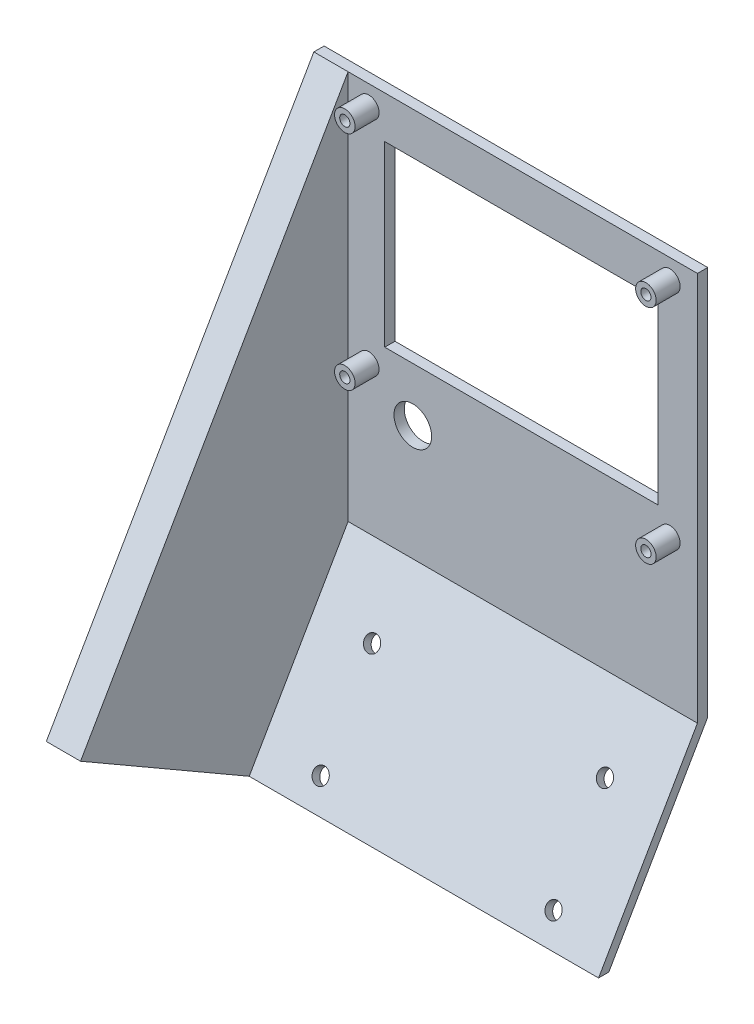
SolidWorks part; units mm, degrees
ref_plane "Front Plane" through (0, 0, 0) normal (0, 0, 1) x (1, 0, 0)
ref_plane "Top Plane" through (0, 0, 0) normal (0, 1, 0) x (1, 0, 0)
ref_plane "Right Plane" through (0, 0, 0) normal (1, 0, 0) x (0, 0, -1)
sketch "Sketch1" plane through (0, 0, 0) normal (0, 0, 1) x (1, 0, 0)
  line L0 (0, 0) -> (0, 113.73)
  line L1 (0, 0) -> (102, 0)
  line L2 (102, 0) -> (102, 113.73)
  line L3 (0, 113.73) -> (102, 113.73)
  line L5 (10.7, 101.42) -> (90.5, 101.42)
  line L6 (10.7, 101.42) -> (10.7, 49.42)
  line L7 (10.7, 49.42) -> (90.5, 49.42)
  line L8 (90.5, 101.42) -> (90.5, 49.42)
  circle A0 centre (6.05, 107.87) radius 3
  circle A1 centre (93.95, 107.87) radius 3
  circle A2 centre (6.05, 42.97) radius 3
  circle A3 centre (93.95, 42.97) radius 3
  circle A4 centre (18.9, 33.699) radius 5.5
  dimension "D7" = 6
  dimension "D10" = 11
  dimension "D1" = 87.9
  dimension "D2" = 64.9
  dimension "D3" = 102
  dimension "D4" = 6.05
  dimension "D5" = 113.73
  dimension "D6" = 5.86
  dimension "D8" = 18.9
  dimension "D9" = 80.031
  dimension "D11" = 12.31
  dimension "D12" = 10.7
  dimension "D13" = 52
  dimension "D14" = 79.8
extrude "Boss-Extrude1" add sketch "Sketch1" along normal blind 3 contours L3 L0 L1 L2 A4 A3 A2 A1 A0 L5 L8 L7 L6 | A0 | A1 region at (51.666, 46.2484, 0)
extrude "Boss-Extrude2" add sketch "Sketch1<3>" along normal blind 10 contours A0 | A2 | A3 | A1
sketch "Sketch1<3>" plane through (0, 0, 0) normal (0, 0, 1) x (1, 0, 0) same geometry as "Sketch1"
sketch "Sketch2" plane through (0, 0, 10) normal (0, 0, 1) x (1, 0, 0)
  circle A0 centre (6.05, 107.87) radius 1.5
  circle A1 centre (93.95, 107.87) radius 1.5
  circle A2 centre (93.95, 42.97) radius 1.5
  circle A3 centre (6.05, 42.97) radius 1.5
  dimension "D1" = 3
extrude "Cut-Extrude1" cut sketch "Sketch2" against normal up to surface (7 mm away) up to face at (96.95, 107.87, 3)
sketch "Sketch3" plane through (102, 0, 0) normal (1, 0, 0) x (0, 0, -1)
  line L0 (-3, 0) -> (-31.8675, -50)
  line L1 (0, 0) -> (-28.8675, -50)
  line L2 (-31.8675, -50) -> (-28.8675, -50)
  line L3 (-3, 0) -> (-3, 113.73) construction
  line L4 (-3, 0) -> (0, 0) construction
  line L5 (-3, 0) -> (0, 0)
  dimension "D1" = 150
  dimension "D2" = 50
extrude "Boss-Extrude3" add sketch "Sketch3" against normal up to surface (102 mm away) up to face at (0, 56.865, 1.5)
sketch "Sketch4" plane through (0, 1.299, 2.25) normal (0, 0.5, 0.866) x (1, 0, 0)
  line L0 (0, -1.5) -> (102, -1.5) construction
  line L1 (0, -1.5) -> (0, -59.235) construction
  line L2 (102, -1.5) -> (102, -59.235) construction
  line L3 (17, -36.5) -> (85, -36.5) construction
  circle A0 centre (17, -21.5) radius 2.25
  circle A1 centre (85, -21.5) radius 2.25
  circle A2 centre (85, -51.5) radius 2.25
  circle A3 centre (17, -51.5) radius 2.25
  dimension "D1" = 4.5
  dimension "D2" = 20
  dimension "D3" = 17
  dimension "D4" = 17
  dimension "D5" = 20
  dimension "D6" = 15
extrude "Cut-Extrude2" cut sketch "Sketch4" against normal through all
sketch "Sketch5" plane through (0, 0, 0) normal (-1, 0, 0) x (0, 0, 1)
  line L0 (31.8675, -50) -> (81.114, -21.5675)
  line L1 (81.114, -21.5675) -> (3, 113.73)
  line L2 (3, 0) -> (31.8675, -50) construction
  line L6 (0, 113.73) -> (0, 0)
  line L7 (0, 0) -> (28.8675, -50)
  line L8 (28.8675, -50) -> (31.8675, -50)
  line L9 (31.8675, -50) -> (3, 0)
  line L10 (3, 0) -> (3, 113.73)
  line L11 (3, 113.73) -> (0, 113.73)
  line L12 (0, 113.73) -> (0, 0)
  line L13 (0, 0) -> (28.8675, -50)
  line L14 (28.8675, -50) -> (31.8675, -50)
  line L17 (3, 113.73) -> (0, 113.73)
  point P4 (83.414, -7.1258)
  point P6 (90.4266, -17.5827)
  dimension "D2" = 90
  dimension "D3" = 30
  dimension "D1" = 0
extrude "Boss-Extrude4" add sketch "Sketch5" along normal blind 10
